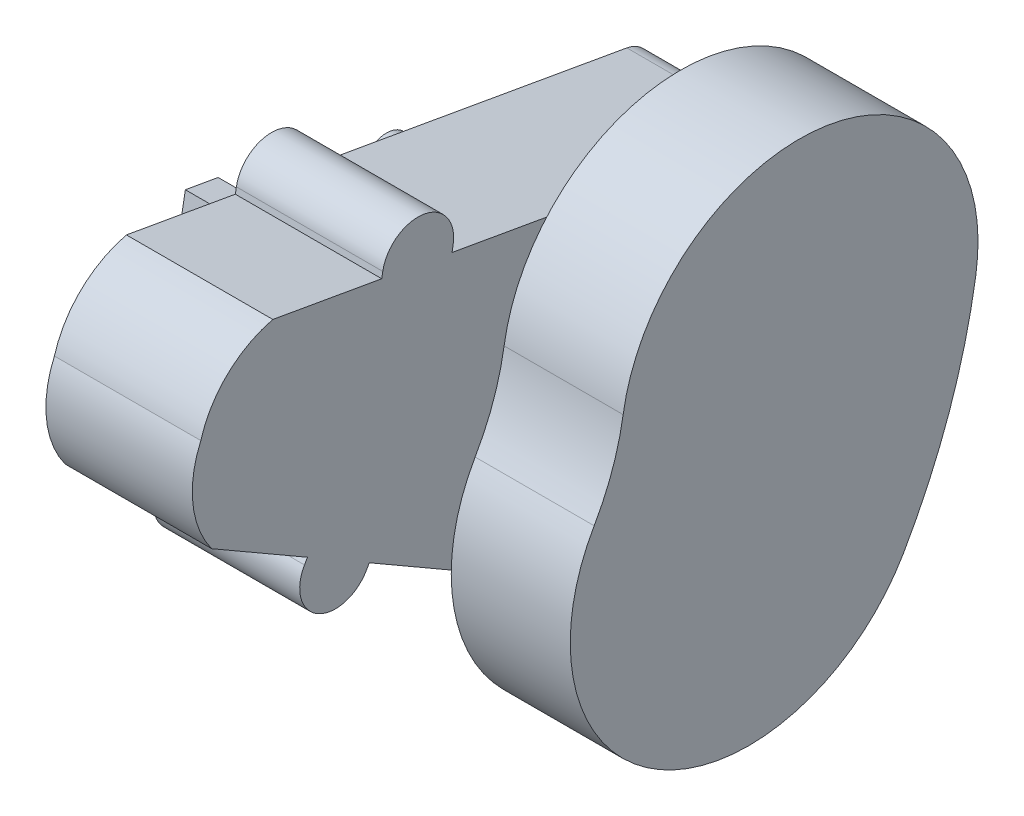
SolidWorks part; units mm, degrees
ref_plane "Front Plane" through (0, 0, 0) normal (0, 0, 1) x (1, 0, 0)
ref_plane "Top Plane" through (0, 0, 0) normal (0, 1, 0) x (1, 0, 0)
ref_plane "Right Plane" through (0, 0, 0) normal (1, 0, 0) x (0, 0, -1)
sketch "Sketch1" plane through (0, 0, 0) normal (1, 0, 0) x (0, 0, -1)
  line L0 (3.1052, 15.25) -> (16, 12.9763) construction
  line L1 (3.1052, 15.25) -> (16, 12.9763) construction
  line L2 (-0.2321, -17.5002) -> (-13.4374, -9.8761) construction
  line L3 (-0.2321, -17.5002) -> (-13.4374, -9.8761) construction
sketch "Sketch2"
sketch_block_instance "Block2-1"
sketch_block "Block2"
sketch "Sketch5" plane through (21.6, 0, 0) normal (1, 0, 0) x (0, 0, -1)
  line L1 (-0.2321, -17.5002) -> (-13.4374, -9.8761) construction
  line L2 (3.1052, 15.25) -> (16, 12.9763) construction
  line B0 (7.625, 13.2069) -> (-7.625, -13.2069)
  line B1 (8.4666, -22.4974) -> (7.9666, -23.3634)
  line B2 (18.3589, -29.3634) -> (18.8589, -28.4974)
  line B3 (18.8589, -28.4974) -> (66.3162, -55.8969)
  line B4 (73.1464, -54.0668) -> (83.3964, -36.3132)
  line B5 (81.5662, -29.4831) -> (34.1089, -2.0836)
  line B6 (34.1089, -2.0836) -> (34.6089, -1.2176)
  line B7 (24.2166, 4.7824) -> (23.7166, 3.9164)
  line B8 (23.7166, 3.9164) -> (7.625, 13.2069)
  line B9 (-7.625, -13.2069) -> (8.4666, -22.4974)
  circle B10 centre (60.6218, -35) radius 1.25
  arc B11 (7.9666, -23.3634) -> (18.3589, -29.3634) centre (13.1628, -26.3634) ccw
  arc B12 (66.3162, -55.8969) -> (73.1464, -54.0668) centre (68.8162, -51.5668) ccw
  arc B13 (83.3964, -36.3132) -> (81.5662, -29.4831) centre (79.0662, -33.8132) ccw
  arc B14 (34.6089, -1.2176) -> (24.2166, 4.7824) centre (29.4128, 1.7824) ccw
  arc B15 (7.625, 13.2069) -> (-7.625, -13.2069) centre (5.7401, -3.3141) ccw
  line B16 (2.6481, 15.0183) -> (-2.6481, -15.0183)
  line B17 (15.6506, -18.2449) -> (15.4769, -19.2297)
  line B18 (27.4683, -20.3287) -> (81.4348, -29.8444)
  line B19 (87.227, -25.7886) -> (90.7868, -5.6)
  line B20 (86.731, 0.1922) -> (32.7645, 9.708)
  line B21 (32.7645, 9.708) -> (32.9382, 10.6928)
  line B22 (21.1205, 12.7766) -> (20.9468, 11.7918)
  line B23 (20.9468, 11.7918) -> (2.6481, 15.0183)
  line B24 (-2.6481, -15.0183) -> (15.6506, -18.2449)
  circle B25 centre (68.9365, -12.1554) radius 1.25
  arc B26 (15.4769, -19.2297) -> (27.2946, -21.3135) centre (21.3858, -20.2716) ccw
  arc B27 (81.4348, -29.8444) -> (87.227, -25.7886) centre (82.303, -24.9204) ccw
  arc B28 (90.7868, -5.6) -> (86.731, 0.1922) centre (85.8628, -4.7318) ccw
  arc B29 (32.9382, 10.6928) -> (21.1205, 12.7766) centre (27.0293, 11.7347) ccw
  arc B30 (2.6481, 15.0183) -> (-2.6481, -15.0183) centre (6.5274, -1.151) ccw
sketch_block_instance "Block2-2"
sketch_block_instance "Block2-3"
sketch "Sketch7" plane through (21.6, 0, 0) normal (1, 0, 0) x (0, 0, -1)
  line L0 (-7.625, -13.2069) -> (8.4666, -22.4974) construction
  line L1 (8.4666, -22.4974) -> (7.9666, -23.3634) construction
  line L2 (18.3589, -29.3634) -> (18.8589, -28.4974) construction
  line L3 (18.8589, -28.4974) -> (66.3162, -55.8969) construction
  line L4 (-7.625, -13.2069) -> (8.4666, -22.4974)
  line L5 (8.4666, -22.4974) -> (7.9666, -23.3634)
  line L6 (18.3589, -29.3634) -> (18.8589, -28.4974)
  line L7 (18.8589, -28.4974) -> (66.3162, -55.8969)
  line L8 (86.731, 0.1922) -> (32.7645, 9.708) construction
  line L9 (32.7645, 9.708) -> (32.9382, 10.6928) construction
  line L10 (21.1205, 12.7766) -> (20.9468, 11.7918) construction
  line L11 (20.9468, 11.7918) -> (2.6481, 15.0183) construction
  line L12 (86.731, 0.1922) -> (32.7645, 9.708)
  line L13 (32.7645, 9.708) -> (32.9382, 10.6928)
  line L14 (21.1205, 12.7766) -> (20.9468, 11.7918)
  line L15 (20.9468, 11.7918) -> (2.6481, 15.0183)
  arc A1 (72.4316, -55.0206) -> (90.8524, -4.4099) centre (0, 0) ccw
  arc A2 (7.625, 13.2069) -> (-7.625, -13.2069) centre (5.7401, -3.3141) ccw construction
  arc A3 (7.9666, -23.3634) -> (18.3589, -29.3634) centre (13.1628, -26.3634) ccw construction
  arc A4 (66.3162, -55.8969) -> (73.1464, -54.0668) centre (68.8162, -51.5668) ccw construction
  arc A5 (-9.4541, 3.441) -> (-7.625, -13.2069) centre (5.7401, -3.3141) ccw
  arc A6 (7.9666, -23.3634) -> (18.3589, -29.3634) centre (13.1628, -26.3634) ccw
  arc A7 (66.3162, -55.8969) -> (72.4316, -55.0206) centre (68.8162, -51.5668) ccw
  arc A8 (90.7868, -5.6) -> (86.731, 0.1922) centre (85.8628, -4.7318) ccw construction
  arc A9 (32.9382, 10.6928) -> (21.1205, 12.7766) centre (27.0293, 11.7347) ccw construction
  arc A10 (2.6481, 15.0183) -> (-2.6481, -15.0183) centre (6.5274, -1.151) ccw construction
  arc A11 (90.8524, -4.4099) -> (86.731, 0.1922) centre (85.8628, -4.7318) ccw
  arc A12 (32.9382, 10.6928) -> (21.1205, 12.7766) centre (27.0293, 11.7347) ccw
  arc A13 (2.6481, 15.0183) -> (-9.4541, 3.441) centre (6.5274, -1.151) ccw
extrude "Boss-Extrude2" add sketch "Sketch7" against normal up to surface (24.6 mm away)
sketch "Sketch8" plane through (-3, 0, 0) normal (-1, 0, 0) x (0, 0, 1)
  line L0 (-20.9468, 11.7918) -> (-2.6481, 15.0183) construction
  line B0 (0, 0) -> (-50.3462, 0.0076) construction
  line B1 (0, 0) -> (-47.3073, -17.2265) construction
  line B2 (0, 0) -> (-48.8268, -8.6095) construction
  line B3 (-48.8268, -8.6095) -> (-50.3462, 0.0076) construction
  circle B4 centre (-50.3462, 0.0076) radius 4
  circle B5 centre (-47.3073, -17.2265) radius 4
sketch_block_instance "Block4-1"
sketch_block "Block4"
sketch "Sketch9" plane through (-3, 0, 0) normal (-1, 0, 0) x (0, 0, 1)
  line L3 (-81.5662, -29.4831) -> (-34.1089, -2.0836) construction
  line B0 (0, 0) -> (-47.3125, -17.2123) construction
  line B1 (0, 0) -> (-38.5625, -32.3677) construction
  line B2 (0, 0) -> (-42.9375, -24.79) construction
  line B3 (-42.9375, -24.79) -> (-47.3125, -17.2123) construction
  circle B4 centre (-47.3125, -17.2123) radius 4
  circle B5 centre (-38.5625, -32.3677) radius 4
sketch_block_instance "Block4-2"
sketch "Sketch10" plane through (-3, 0, 0) normal (-1, 0, 0) x (0, 0, 1)
  arc A0 (-54.3462, 0.0082) -> (-41.6263, -34.9393) centre (0, 0) ccw
  circle A1 centre (-50.3462, 0.0076) radius 4 construction
  circle A2 centre (-38.5625, -32.3677) radius 4 construction
  arc A3 (-41.6263, -34.9393) -> (-35.4987, -29.7961) centre (-38.5625, -32.3677) ccw
  arc A4 (-46.3462, 0.007) -> (-54.3462, 0.0082) centre (-50.3462, 0.0076) ccw
  arc A5 (-35.4987, -29.7961) -> (-46.3462, 0.007) centre (0, 0) cw
  circle A6 centre (-47.3073, -17.2265) radius 4 construction
extrude "Boss-Extrude3" add sketch "Sketch10" along normal up to surface (4 mm away)
sketch "Sketch11" plane through (-3, 0, 0) normal (-1, 0, 0) x (0, 0, 1)
  line L0 (-81.5662, -29.4831) -> (-34.1089, -2.0836) construction
  line L24 (-2.6481, 15.0183) -> (-20.9468, 11.7918) construction
  line B0 (-27.205, -12.0319) -> (-30.6518, -12.6397)
  line B1 (-24.6415, -15.0526) -> (-24.8881, -13.6542)
  line B2 (-19.1266, -14.0802) -> (-24.6415, -15.0526)
  line B3 (-19.7204, -10.7122) -> (-19.1266, -14.0802)
  line B4 (-14.1589, -7.7007) -> (-18.0981, -8.3952)
  line B5 (-15.8954, 2.1474) -> (-14.1589, -7.7007)
  line B6 (-19.8346, 1.4528) -> (-15.8954, 2.1474)
  line B7 (-22.7454, 6.4432) -> (-22.1515, 3.0751)
  line B8 (-28.2603, 5.4708) -> (-22.7454, 6.4432)
  line B9 (-28.0137, 4.0723) -> (-28.2603, 5.4708)
  line B10 (-33.0829, 1.1477) -> (-29.6361, 1.7554)
  line B11 (-30.6518, -12.6397) -> (-33.0829, 1.1477)
  line B12 (-15.0488, -2.6535) -> (0, 0)
  arc B13 (-24.8881, -13.6542) -> (-27.205, -12.0319) centre (-26.8577, -14.0015) ccw
  arc B14 (-18.0981, -8.3952) -> (-19.7204, -10.7122) centre (-17.7508, -10.3649) ccw
  arc B15 (-22.1515, 3.0751) -> (-19.8346, 1.4528) centre (-20.1819, 3.4224) ccw
  arc B16 (-29.6361, 1.7554) -> (-28.0137, 4.0723) centre (-29.9834, 3.725) ccw
  line B17 (-21.4492, -20.6109) -> (-24.4803, -22.3609)
  line B18 (-18.0071, -22.5727) -> (-18.7171, -21.343)
  line B19 (-13.1574, -19.7727) -> (-18.0071, -22.5727)
  line B20 (-14.8674, -16.8109) -> (-13.1574, -19.7727)
  line B21 (-10.6712, -12.0789) -> (-14.1353, -14.0789)
  line B22 (-15.6712, -3.4186) -> (-10.6712, -12.0789)
  line B23 (-19.1353, -5.4186) -> (-15.6712, -3.4186)
  line B24 (-23.5774, -1.7248) -> (-21.8674, -4.6866)
  line B25 (-28.4271, -4.5248) -> (-23.5774, -1.7248)
  line B26 (-31.4803, -10.2366) -> (-28.4492, -8.4866)
  line B27 (-24.4803, -22.3609) -> (-31.4803, -10.2366)
  line B28 (-13.2337, -7.6405) -> (0, 0)
  arc B29 (-18.7171, -21.343) -> (-21.4492, -20.6109) centre (-20.4492, -22.343) ccw
  arc B30 (-14.1353, -14.0789) -> (-14.8674, -16.8109) centre (-13.1353, -15.8109) ccw
sketch_block_instance "Block7-1"
sketch_block "Block7"
sketch_block_instance "Block7-2"
sketch "Sketch13" plane through (-3, 0, 0) normal (-1, 0, 0) x (0, 0, 1)
  line L0 (-7.625, 13.2069) -> (7.625, -13.2069) construction
  line L1 (-10.6712, -12.0789) -> (-14.1353, -14.0789) construction
  line L2 (-14.8674, -16.8109) -> (-13.1574, -19.7727) construction
  line L3 (-13.1574, -19.7727) -> (-18.0071, -22.5727) construction
  line L4 (-18.0071, -22.5727) -> (-18.7171, -21.343) construction
  line L5 (-21.4492, -20.6109) -> (-24.4803, -22.3609) construction
  line L6 (-19.8346, 1.4528) -> (-15.8954, 2.1474) construction
  line L7 (-22.7454, 6.4432) -> (-22.1515, 3.0751) construction
  line L8 (-28.2603, 5.4708) -> (-22.7454, 6.4432) construction
  line L9 (-28.0137, 4.0723) -> (-28.2603, 5.4708) construction
  line L10 (-33.0829, 1.1477) -> (-29.6361, 1.7554) construction
  line L11 (-10.6712, -12.0789) -> (-14.1353, -14.0789)
  line L12 (-14.8674, -16.8109) -> (-13.1574, -19.7727)
  line L13 (-13.1574, -19.7727) -> (-18.0071, -22.5727)
  line L14 (-18.0071, -22.5727) -> (-18.7171, -21.343)
  line L15 (-21.4492, -20.6109) -> (-24.4803, -22.3609)
  line L16 (-19.8346, 1.4528) -> (-15.8954, 2.1474)
  line L17 (-22.7454, 6.4432) -> (-22.1515, 3.0751)
  line L18 (-28.2603, 5.4708) -> (-22.7454, 6.4432)
  line L19 (-28.0137, 4.0723) -> (-28.2603, 5.4708)
  line L20 (-33.0829, 1.1477) -> (-29.6361, 1.7554)
  line L21 (-15.8954, 2.1474) -> (-14.1589, -7.7007) construction
  arc A0 (-33.0829, 1.1477) -> (-24.4803, -22.3609) centre (0.0355, -0.0615) ccw
  arc A1 (-14.1353, -14.0789) -> (-14.8674, -16.8109) centre (-13.1353, -15.8109) ccw construction
  arc A2 (-18.7171, -21.343) -> (-21.4492, -20.6109) centre (-20.4492, -22.343) ccw construction
  arc A3 (-22.1515, 3.0751) -> (-19.8346, 1.4528) centre (-20.1819, 3.4224) ccw construction
  arc A4 (-29.6361, 1.7554) -> (-28.0137, 4.0723) centre (-29.9834, 3.725) ccw construction
  arc A5 (-14.1353, -14.0789) -> (-14.8674, -16.8109) centre (-13.1353, -15.8109) ccw
  arc A6 (-18.7171, -21.343) -> (-21.4492, -20.6109) centre (-20.4492, -22.343) ccw
  arc A7 (-22.1515, 3.0751) -> (-19.8346, 1.4528) centre (-20.1819, 3.4224) ccw
  arc A8 (-29.6361, 1.7554) -> (-28.0137, 4.0723) centre (-29.9834, 3.725) ccw
  arc A10 (-10.6712, -12.0789) -> (-15.8954, 2.1474) centre (26.3924, 9.6039) cw
extrude "Boss-Extrude4" add sketch "Sketch13" along normal up to surface (10.2 mm away)
sketch "Sketch14" plane through (43.6, 0, 0) normal (1, 0, 0) x (0, 0, -1)
  line L0 (0, 0) -> (39.5075, -6.2574) construction
  line L1 (20.7379, 12.1555) -> (2.3856, 15.0622) construction
  line L2 (0, 0) -> (34.641, -20) construction
  line L3 (81.5662, -29.4831) -> (34.1089, -2.0836) construction
  arc A0 (98.7688, -15.6434) -> (39.5075, -6.2574) centre (69.1382, -10.9504) ccw
  circle A1 centre (69.1382, -10.9504) radius 30 construction
  arc A2 (34.641, -20) -> (86.6025, -50) centre (60.6218, -35) ccw
  arc A3 (86.6025, -50) -> (98.7688, -15.6434) centre (0, 0) ccw
  arc A4 (34.641, -20) -> (39.5075, -6.2574) centre (0, 0) ccw
  point P1 (0, 0)
extrude "Boss-Extrude5" add sketch "Sketch14" against normal up to surface (20 mm away) separate body
